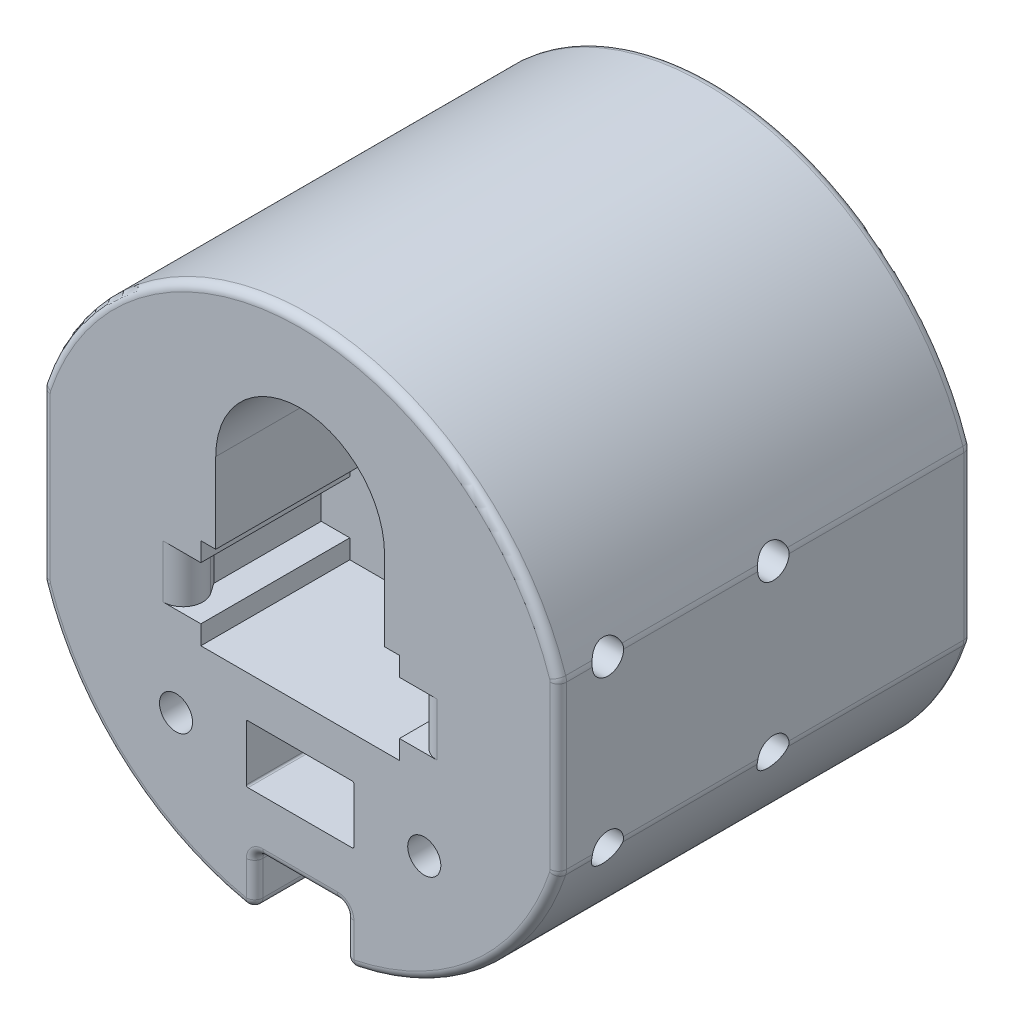
SolidWorks part; units mm, degrees
ref_plane "前视基准面" through (0, 0, 0) normal (0, 0, 1) x (1, 0, 0)
ref_plane "上视基准面" through (0, 0, 0) normal (0, 1, 0) x (1, 0, 0)
ref_plane "右视基准面" through (0, 0, 0) normal (1, 0, 0) x (0, 0, -1)
sketch "草图1" plane through (0, 0, 0) normal (0, 0, 1) x (1, 0, 0)
  line L0 (-10, 17.7) -> (10, 17.7) construction
  circle A0 centre (0, 0) radius 16.4
  circle A1 centre (0, -2.8) radius 8.5 construction
  point P7 (0, 17.7)
  dimension "D1" = 32.8
  dimension "D3" = 17
  dimension "D4" = 20.5
  dimension "D2" = 17.7
  dimension "D5" = 20
extrude "凸台-拉伸1" add sketch "草图1" against normal blind 25
sketch "草图2" plane through (0, 0, 0) normal (0, 0, 1) x (1, 0, 0)
  line L1 (6, -3.75) -> (-6, -3.75)
  line L2 (6, -3.75) -> (6, 1.75)
  line L3 (6, 1.75) -> (-6, 1.75)
  line L4 (-6, -3.75) -> (-6, 1.75)
  line L5 (6, -3.75) -> (-6, 1.75) construction
  line L6 (6, 1.75) -> (-6, -3.75) construction
  line L7 (3.25, -9.75) -> (-3.25, -9.75)
  line L8 (3.25, -9.75) -> (3.25, -6.25)
  line L9 (3.25, -6.25) -> (-3.25, -6.25)
  line L10 (-3.25, -9.75) -> (-3.25, -6.25)
  line L11 (3.25, -9.75) -> (-3.25, -6.25) construction
  line L12 (3.25, -6.25) -> (-3.25, -9.75) construction
  point P0 (0, -1)
  point P5 (0, -8)
  dimension "D1" = 12
  dimension "D2" = 5.5
  dimension "D3" = 6.5
  dimension "D4" = 3.5
  dimension "D5" = 7
  dimension "D6" = 1
extrude "切除-拉伸1" cut sketch "草图2" against normal through all
sketch "草图4" plane through (0, 0, 0) normal (0, 0, 1) x (1, 0, 0)
  line L0 (3.05, -1) -> (-3.05, -1) construction
  line L1 (6, 1.75) -> (-6, -3.75) construction
  line L2 (3.05, -5.6) -> (-3.05, -5.6) construction
  line L3 (3.05, 3.6) -> (-3.05, 3.6) construction
  arc A0 (3.05, -5.6) -> (3.05, 3.6) centre (3.05, -1) ccw construction
  arc A1 (-3.05, 3.6) -> (-3.05, -5.6) centre (-3.05, -1) ccw construction
  point P4 (0, -1)
  point P9 (-7.65, -1)
  point P10 (7.65, -1)
  dimension "D1" = 15.3
  dimension "D2" = 9.2
sketch "草图5" plane through (0, 0, -25) normal (0, 0, -1) x (-1, 0, 0)
  line L1 (10, -10.9) -> (-10, -10.9)
  line L2 (10, -10.9) -> (10, -5.1)
  line L3 (10, -5.1) -> (-10, -5.1)
  line L4 (-10, -10.9) -> (-10, -5.1)
  line L5 (10, -10.9) -> (-10, -5.1) construction
  line L6 (10, -5.1) -> (-10, -10.9) construction
  point P0 (0, -8)
  dimension "D1" = 20
  dimension "D2" = 5.8
extrude "切除-拉伸2" cut sketch "草图5" against normal offset from surface (21.4 mm away) 3.6 up to face at (0, -1, 0)
fillet "圆角1" radius 1.5 4 edges at (-10, -10.9, -14.3) (-10, -5.1, -14.3) (10, -5.1, -14.3) (10, -10.9, -14.3)
sketch "草图6" plane through (0, 0, -3.6) normal (0, 0, -1) x (-1, 0, 0)
  line L0 (7.5, -8) -> (-7.5, -8) construction
  circle A0 centre (-7.5, -8) radius 1
  circle A1 centre (7.5, -8) radius 1
  point P3 (0, -8)
  dimension "D1" = 15
  dimension "D2" = 2
extrude "切除-拉伸3" cut sketch "草图6" against normal through all
sketch "草图8" plane through (0, 0, 0) normal (0, 0, 1) x (1, 0, 0)
  line L0 (-5.1, 6.6) -> (-5.1, 1.5)
  line L2 (-5.1, 1.5) -> (5.1, 1.5)
  line L3 (5.1, 1.5) -> (5.1, 6.6)
  arc A0 (5.1, 6.6) -> (-5.1, 6.6) centre (0, 6.6) ccw
  dimension "D1" = 10.2
  dimension "D2" = 7.6
  dimension "D3" = 5.1
extrude "切除-拉伸4" cut sketch "草图8" against normal blind 20.8
sketch "草图10" plane through (0, 0, 0) normal (0, 0, 1) x (1, 0, 0)
  line L0 (-15.6, -5.0596) -> (-15.6, 5.0596)
  line L1 (15.6, 5.0596) -> (15.6, -5.0596)
  circle A0 centre (0, 0) radius 16.4 construction
  arc A1 (15.6, -5.0596) -> (15.6, 5.0596) centre (0, 0) ccw
  arc A2 (-15.6, 5.0596) -> (-15.6, -5.0596) centre (0, 0) ccw
  dimension "D1" = 31.2
extrude "切除-拉伸5" cut sketch "草图10" against normal through all
sketch "草图11" plane through (15.6, 0, 0) normal (1, 0, 0) x (0, 0, -1)
  line L0 (0, 5.0596) -> (0, -5.0596) construction
  line L1 (13, -5.08) -> (3, -5.08) construction
  line L2 (13, -5.08) -> (13, 4.92) construction
  line L3 (13, 4.92) -> (3, 4.92) construction
  line L4 (3, -5.08) -> (3, 4.92) construction
  line L5 (13, -5.08) -> (3, 4.92) construction
  line L6 (13, 4.92) -> (3, -5.08) construction
  circle A0 centre (3, 4.92) radius 0.95
  circle A1 centre (13, 4.92) radius 0.95
  circle A2 centre (13, -5.08) radius 0.95
  circle A3 centre (3, -5.08) radius 0.95
  point P2 (8, -0.08)
  dimension "D1" = 4.92
  dimension "D2" = 10
  dimension "D3" = 1.9
  dimension "D4" = 10
  dimension "D5" = 3
extrude "切除-拉伸6" cut sketch "草图11" against normal blind 4.5
mirror "镜向1" about plane through (0, 0, 0) normal (1, 0, 0) of "切除-拉伸6"
fillet "圆角2" radius 1 12 edges at (-15.6, 5.0596, -19.4698) (-15.6, 5.0596, -8) (-15.6, 5.0596, -1.0302) (-15.6, -5.0596, -1.0251) (-15.6, -5.0596, -19.4749) (-15.6, -5.0596, -8) (15.6, -5.0596, -19.4749) (15.6, -5.0596, -8) (15.6, -5.0596, -1.0251) (15.6, 5.0596, -19.4698) (15.6, 5.0596, -8) (15.6, 5.0596, -1.0302)
sketch "草图12" plane through (0, 0, -20.8) normal (0, 0, 1) x (1, 0, 0)
  line L0 (2.35, 6.6) -> (-2.35, 6.6) construction
  circle A0 centre (-2, 6.6) radius 0.35 construction
  circle A1 centre (2, 6.6) radius 0.35 construction
  arc A2 (5.1, 6.6) -> (-5.1, 6.6) centre (0, 6.6) ccw construction
  circle A3 centre (-2, 6.6) radius 0.55
  circle A4 centre (2, 6.6) radius 0.55
  point P5 (0, 6.6)
  dimension "D1" = 4.7
  dimension "D2" = 0.7
  dimension "D3" = 0.2
extrude "切除-拉伸7" cut sketch "草图12" against normal through all
ref_plane "基准面1" through (0, -1, 0) normal (0, -1, 0) x (-1, 0, 0)
sketch "草图13" plane through (0, -1, 0) normal (0, 1, 0) x (1, 0, 0)
  line L0 (-8.2808, 0) -> (-6, 0)
  line L1 (-6, 0) -> (-6, 25)
  line L2 (-6, 25) -> (-6, 0) construction
  line L3 (-6, 25) -> (-7.725, 25)
  line L4 (-7.725, 2.5099) -> (-7.2919, 1.8797)
  line L5 (-7.725, 2.5099) -> (-7.725, 25)
  line L6 (0, 0) -> (0, 25) construction
  line L7 (-15.5481, 0) -> (15.5481, 0) construction
  line L8 (15.5481, 25) -> (-15.5481, 25) construction
  line L9 (-7.2919, 1.8797) -> (-6, 0) construction
  line L10 (6, 25) -> (7.725, 25)
  line L11 (6, 0) -> (6, 25)
  line L12 (8.2808, 0) -> (6, 0)
  line L13 (7.725, 2.5099) -> (7.2919, 1.8797)
  line L14 (7.725, 2.5099) -> (7.725, 25)
  arc A0 (-8.2808, 0) -> (-7.2919, 1.8797) centre (-8.2808, 1.2) ccw
  arc A1 (8.2808, 0) -> (7.2919, 1.8797) centre (8.2808, 1.2) cw
  dimension "D1" = 34.5
  dimension "D3" = 1.2
  dimension "D2" = 15.45
extrude "切除-拉伸8" cut sketch "草图13" along normal mid plane 3.2
sketch "草图14" plane through (0, 0, -25) normal (0, 0, -1) x (-1, 0, 0)
  line L0 (-7.725, -3.75) -> (-7.725, 1.75)
  line L1 (-7.725, 1.75) -> (7.725, 1.75)
  line L2 (7.725, 1.75) -> (7.725, -3.75)
  line L3 (7.725, -3.75) -> (-7.725, -3.75)
  line L4 (6, -3.75) -> (-6, -3.75) construction
  line L5 (7.725, 0.6) -> (7.725, -2.6) construction
  line L6 (-7.725, 0.6) -> (-7.725, -2.6) construction
  line L7 (-6, 1.75) -> (6, 1.75) construction
extrude "凸台-拉伸2" add sketch "草图14" against normal blind 16
sketch "草图15" plane through (0, 0, -9) normal (0, 0, 1) x (1, 0, 0)
  line L0 (-5.1, 6.6) -> (-5.1, 1.75)
  line L1 (-5.1, 1.75) -> (-1.5772, 1.75)
  line L2 (-5.1, 1.75) -> (5.1, 1.75) construction
  line L3 (1.5772, 1.75) -> (5.1, 1.75)
  line L4 (5.1, 1.75) -> (5.1, 6.6)
  arc A0 (-5.1, 6.6) -> (-1.5772, 1.75) centre (0, 6.6) ccw
  arc A1 (1.5772, 1.75) -> (5.1, 6.6) centre (0, 6.6) ccw
extrude "凸台-拉伸3" add sketch "草图15" against normal up to surface (11.8 mm away) up to face at (-1.45, 6.6, -20.8)
sketch "草图16" plane through (0, 0, -20.8) normal (0, 0, 1) x (1, 0, 0)
  line L0 (-1.5772, 1.75) -> (1.5772, 1.75) construction
  line L1 (-1.5772, 1.75) -> (1.5772, 1.75)
  arc A0 (-1.5772, 1.75) -> (1.5772, 1.75) centre (0, 6.6) ccw
extrude "切除-拉伸9" cut sketch "草图16" along normal up to surface (11.8 mm away) up to face at (0, 0.392, -9)
fillet "圆角3" radius 0.5 1 edges at (5.1, 6.6, -20.8)
chamfer "倒角3" distance 0.8 angle 45 1 edges at (0, 1.5, -9)
sketch "草图17" plane through (0, 0, -9) normal (0, 0, 1) x (1, 0, 0)
  line L0 (-1.5, -1) -> (1.5, -1) construction
  line L1 (-1.5, 0.25) -> (1.5, 0.25)
  line L2 (-1.5, -2.25) -> (1.5, -2.25)
  line L3 (-8.2808, 0.6) -> (-8.2808, -2.6) construction
  arc A0 (-1.5, 0.25) -> (-1.5, -2.25) centre (-1.5, -1) ccw
  arc A1 (1.5, -2.25) -> (1.5, 0.25) centre (1.5, -1) ccw
  point P2 (0, -1)
  point P9 (-8.2808, -1)
  dimension "D2" = 1.25
  dimension "D1" = 3
extrude "切除-拉伸10" cut sketch "草图17" against normal through all
fillet "圆角7" radius 0.1 4 edges at (-3.25, -6.25, -1.8) (-3.25, -9.75, -1.8) (3.25, -9.75, -1.8) (3.25, -6.25, -1.8)
sketch "草图18" plane through (0, 0, -25) normal (0, 0, -1) x (-1, 0, 0)
  line L0 (-2, 6.6) -> (2, 6.6) construction
  line L1 (-2, 9.1) -> (2, 9.1)
  line L2 (-2, 4.1) -> (2, 4.1)
  arc A0 (-2, 9.1) -> (-2, 4.1) centre (-2, 6.6) ccw
  arc A1 (2, 4.1) -> (2, 9.1) centre (2, 6.6) ccw
  point P4 (0, 6.6)
  dimension "D1" = 2.5
extrude "切除-拉伸11" cut sketch "草图18" against normal blind 2
sketch "草图20" plane through (0, 0, 0) normal (0, 0, 1) x (1, 0, 0)
  line L0 (3.25, -9.65) -> (3.25, -6.35) construction
  line L2 (2.75, -15) -> (2.75, -13)
  line L3 (2.75, -13) -> (-2.75, -13)
  line L4 (-2.75, -15) -> (-2.75, -13)
  line L5 (2.75, -15) -> (-2.75, -13) construction
  line L6 (2.75, -13) -> (-2.75, -15) construction
  line L7 (-2.75, -15) -> (-2.75, -16.1678)
  line L8 (2.75, -15) -> (2.75, -16.1678)
  arc A0 (-15.5481, -5.2171) -> (15.5481, -5.2171) centre (0, 0) ccw construction
  arc A1 (-2.75, -16.1678) -> (2.75, -16.1678) centre (0, 0) ccw
  point P0 (0, -14)
  point P7 (3.25, -8)
  dimension "D1" = 6
  dimension "D2" = 5.5
  dimension "D3" = 2
extrude "切除-拉伸12" cut sketch "草图20" against normal blind 8
extrude "切除-拉伸14" cut sketch "草图20<2>" along normal offset from surface (12 mm away) 5 from surface up to face at (0, -14.6419, -8) starting at face at (0, 6.6, -25)
sketch "草图20<2>" plane through (0, 0, 0) normal (0, 0, 1) x (1, 0, 0) same geometry as "草图20"
sketch "草图23" plane through (0, 0, -25) normal (0, 0, -1) x (-1, 0, 0)
  line L11 (-4.5, 6.6) -> (-4.5, -5.1)
  line L12 (8.5, -5.1) -> (-8.5, -5.1) construction
  line L13 (-4.5, -5.1) -> (4.5, -5.1)
  line L14 (8.5, -5.1) -> (-8.5, -5.1) construction
  line L15 (4.5, -5.1) -> (4.5, 6.6)
  line L16 (-2, 4.1) -> (2, 4.1) construction
  line L17 (-2, 4.1) -> (2, 4.1)
  arc A13 (-2, 9.1) -> (-2, 4.1) centre (-2, 6.6) ccw construction
  arc A14 (2, 4.1) -> (2, 9.1) centre (2, 6.6) ccw construction
  arc A15 (-2, 9.1) -> (-2, 4.1) centre (-2, 6.6) ccw construction
  arc A16 (2, 4.1) -> (4.5, 6.6) centre (2, 6.6) ccw
  arc A17 (-4.5, 6.6) -> (-2, 4.1) centre (-2, 6.6) ccw
sketch "草图25" plane through (0, 0, -13) normal (0, 0, -1) x (-1, 0, 0)
  line L0 (-1.27, -14.65) -> (1.27, -14.65) construction
  line L1 (-1.27, -13.8) -> (1.27, -13.8)
  line L2 (-1.27, -15.5) -> (1.27, -15.5)
  line L3 (-2.75, -13) -> (2.75, -13) construction
  arc A0 (-1.27, -13.8) -> (-1.27, -15.5) centre (-1.27, -14.65) ccw
  arc A1 (1.27, -15.5) -> (1.27, -13.8) centre (1.27, -14.65) ccw
  point P2 (0, -14.65)
  dimension "D2" = 0.85
  dimension "D1" = 2.54
  dimension "D3" = 1.65
extrude "切除-拉伸15" cut sketch "草图25" against normal through all
sketch "草图27" plane through (0, 0, -25) normal (0, 0, -1) x (-1, 0, 0)
  line L0 (-8.5, -10.9) -> (8.5, -10.9) construction
  line L1 (-2.75, -13) -> (2.75, -13)
  line L2 (-2.75, -13) -> (-2.75, -10.9)
  line L3 (-2.75, -10.9) -> (2.75, -10.9)
  line L4 (2.75, -13) -> (2.75, -10.9)
  line L5 (2.75, -13) -> (2.75, -16.1678) construction
extrude "切除-拉伸16" cut sketch "草图27" against normal blind 2.5
fillet "圆角14" radius 0.8 2 edges at (0, -10.9, -22.5) (0, -13, -22.5)
fillet "圆角10" radius 0.5 12 edges at (2.75, -16.1678, -4) (-2.75, -16.1678, -4) (-2.75, -16.1678, -19) (2.75, -16.1678, -19) (-2.75, -13, -17.35) (2.75, -13, -17.35) (-2.75, -11.1343, -22.2657) (-2.75, -11.95, -22.5) (-2.75, -12.7657, -22.2657) (2.75, -11.1343, -22.2657) (2.75, -11.95, -22.5) (2.75, -12.7657, -22.2657)
extrude "切除-拉伸18" cut sketch "草图23" against normal blind 2
fillet "圆角15" radius 1 5 edges at (0, -2.25, -23) (-2.75, -1, -23) (0, 0.25, -23) (0, -5.1, -23) (2.75, -1, -23)
fillet "圆角16" radius 0.5 34 edges at (-2.6962, -10.9, -22.4172) (2.6962, -10.9, -22.4172) (4.5, 0.75, -25) (3.7678, 8.3678, -25) (0, 9.1, -25) (-3.7678, 8.3678, -25) (-6.5, -5.1, -25) (-9.5607, -5.5393, -25) (-10, -8, -25) (-9.5607, -10.4607, -25) (6.5, -5.1, -25) (9.5607, -5.5393, -25) (10, -8, -25) (9.5607, -10.4607, -25) (-2.75, -13.2322, -25) (-2.9346, -15.9523, -25) (-10.8933, -12.2596, -25) (-15.5869, -5.0601, -25) (-15.6, 0, -25) (-15.5869, 5.0601, -25) (0, 16.4, -25) (15.5869, 5.0601, -25) (15.6, 0, -25) (15.5869, -5.0601, -25) (10.8933, -12.2596, -25) (2.9346, -15.9523, -25) (-2.75, -10.9, -23.8623) (2.75, -10.9, -23.8623) (-4.5, 0.75, -25) (-5.625, -10.9, -25) (5.625, -10.9, -25) (2.75, -13.2322, -25) (-4.5, -5.1, -23.5) (4.5, -5.1, -23.5)
fillet "圆角17" radius 0.5 18 edges at (-2.75, -14.2822, 0) (-2.9346, -15.9523, 0) (-10.8933, -12.2596, 0) (-15.5869, -5.0601, 0) (-15.6, 0, 0) (-15.5869, 5.0601, 0) (0, 16.4, 0) (15.5869, 5.0601, 0) (2.75, -14.2822, 0) (2.9346, -15.9523, 0) (10.8933, -12.2596, 0) (15.5869, -5.0601, 0) (15.6, 0, 0) (0, -13, 0) (2.75, -13, -4) (-2.75, -13, -4) (0, -16.4, -13) (0, -16.4, -8)
